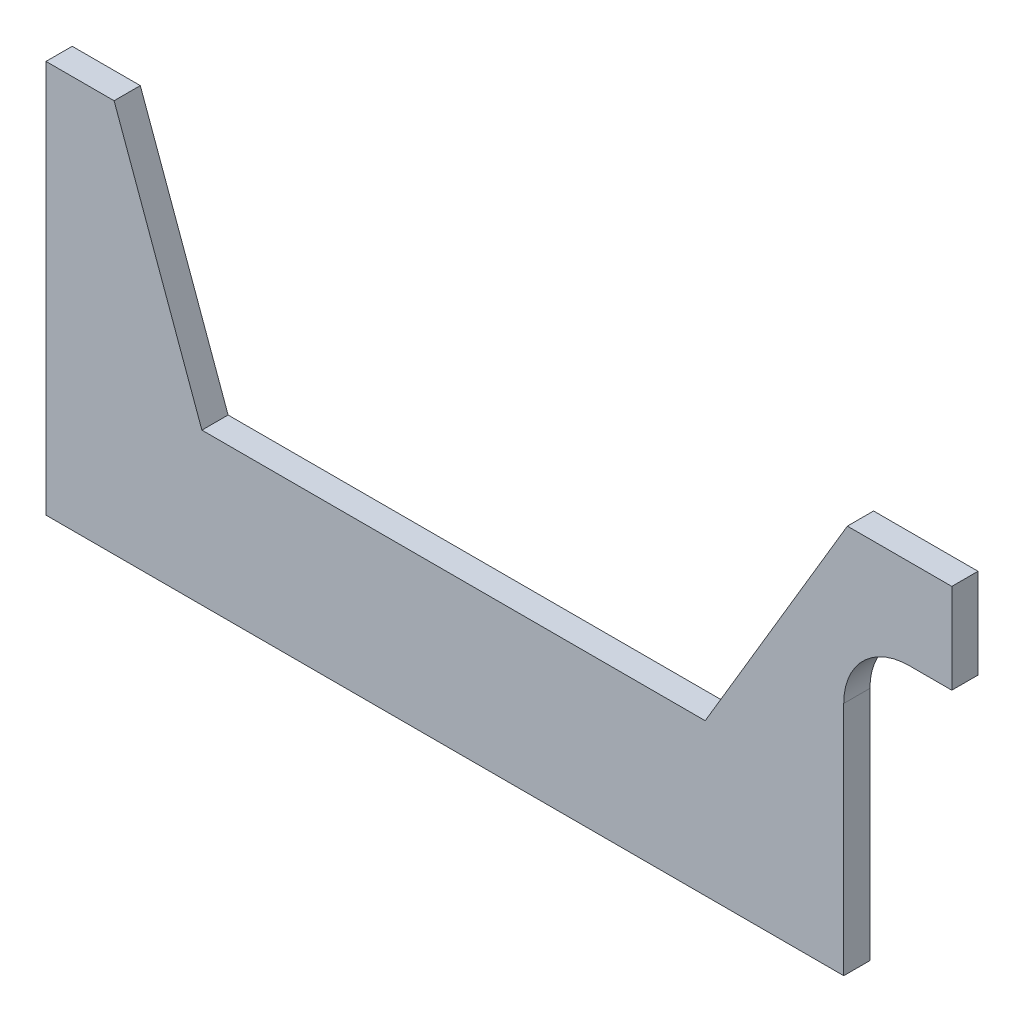
SolidWorks part; units mm, degrees
ref_plane "Front Plane" through (0, 0, 0) normal (0, 0, 1) x (1, 0, 0)
ref_plane "Top Plane" through (0, 0, 0) normal (0, 1, 0) x (1, 0, 0)
ref_plane "Right Plane" through (0, 0, 0) normal (1, 0, 0) x (0, 0, -1)
sketch "Sketch1" plane through (0, 0, 0) normal (0, 0, 1) x (1, 0, 0)
  line L2 (-60.75, -30) -> (-60.75, 30)
  line L11 (61.0497, 16) -> (77.5497, 16)
  line L18 (61.0497, -30) -> (61.0497, 16)
  line L21 (77.5497, 29.7321) -> (77.5497, 16)
  line L23 (-60.75, 30) -> (-50.3529, 30)
  line L24 (-50.3529, 30) -> (-36.9454, -6.8552)
  line L25 (-36.9454, -6.8552) -> (39.8971, -6.8552)
  line L26 (39.8971, -6.8552) -> (61.6068, 29.7321)
  line L27 (61.6068, 29.7321) -> (77.5497, 29.7321)
  line L29 (-60.75, -30) -> (61.0497, -30)
  point P13 (-60.75, 0)
  dimension "D1" = 138.3
  dimension "D2" = 16.5
  dimension "D3" = 46
  dimension "D4" = 60
extrude "Boss-Extrude1" add sketch "Sketch1" along normal mid plane 4
fillet "Fillet1" radius 10 1 edges at (61.0497, 16, 0)
equation "\"wall_thick_ness\"=4"
equation "\"D1@Boss-Extrude1\"=\"wall_thick_ness\""
equation "\"back_boost\"=7"
equation "\"D1@Sketch1\"=\"back_boost\"+131.30mm"
